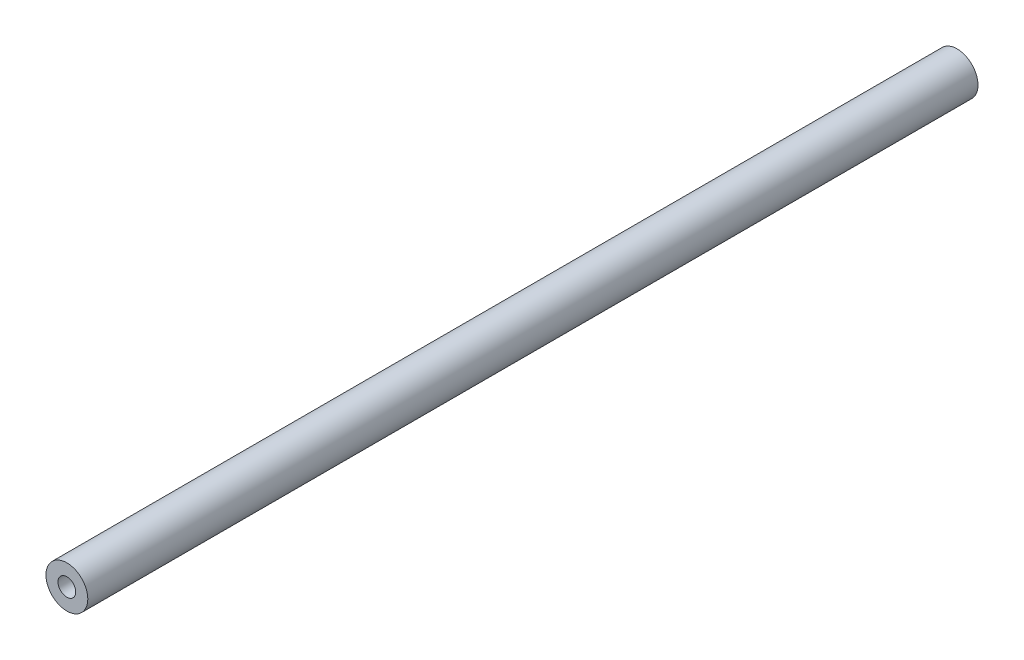
SolidWorks part; units mm, degrees
material "7075-T6, Plate (SS)"
ref_plane "Front Plane" through (0, 0, 0) normal (0, 0, 1) x (1, 0, 0)
ref_plane "Top Plane" through (0, 0, 0) normal (0, 1, 0) x (1, 0, 0)
ref_plane "Right Plane" through (0, 0, 0) normal (1, 0, 0) x (0, 0, -1)
sketch "Sketch1" plane through (0, 0, 0) normal (0, 0, 1) x (1, 0, 0)
  circle A1 centre (0, 0) radius 4.7625
  dimension "D1" = 9.525
extrude "Boss-Extrude1" add sketch "Sketch1" against normal blind 202.692
sketch "Sketch5" plane through (0, 0, -202.692) normal (0, 0, -1) x (-1, 0, 0)
  point P0 (0, 0)
hole_wizard "#10-32 Tapped Hole1" positions "Sketch5" profile "Sketch6" tap size "#10-32" standard "ANSI Inch"
sketch "Sketch6" plane through (0, 0, -202.692) normal (1, 0, 0) x (0, 1, 0)
  line L0 (0, 0) -> (0, 20.2633)
  line L1 (0, 20.2633) -> (2.0193, 19.05)
  line L2 (2.0193, 19.05) -> (2.0193, 0)
  line L5 (2.0193, 0) -> (0, 0)
  line L10 (0, 20.2633) -> (-2.0193, 19.05) construction
  line L11 (0, -6.35) -> (0, 107.95) construction
  dimension "Tap Drill Dia." = 4.0386
  dimension "Tap Drill Depth" = 19.05
  dimension "Drill Angle" = 118
cosmetic thread "Hole Thread1" parameters "D1"=9.652, "D2"=4.826
hole_wizard "#10-32 Tapped Hole4" positions "Sketch11" profile "Sketch12" tap size "#10-32" standard "ANSI Inch"
sketch "Sketch11" plane through (0, 0, 0) normal (0, 0, 1) x (1, 0, 0)
  point P0 (0, 0)
sketch "Sketch12" plane through (0, 0, 0) normal (1, 0, 0) x (0, -1, 0)
  line L0 (0, 0) -> (0, 20.2633)
  line L1 (0, 20.2633) -> (2.0193, 19.05)
  line L2 (2.0193, 19.05) -> (2.0193, 0)
  line L5 (2.0193, 0) -> (0, 0)
  line L10 (0, 20.2633) -> (-2.0193, 19.05) construction
  line L11 (0, -6.35) -> (0, 107.95) construction
  dimension "Tap Drill Dia." = 4.0386
  dimension "Tap Drill Depth" = 19.05
  dimension "Drill Angle" = 118
cosmetic thread "Hole Thread4" parameters "D1"=9.652, "D2"=4.826
